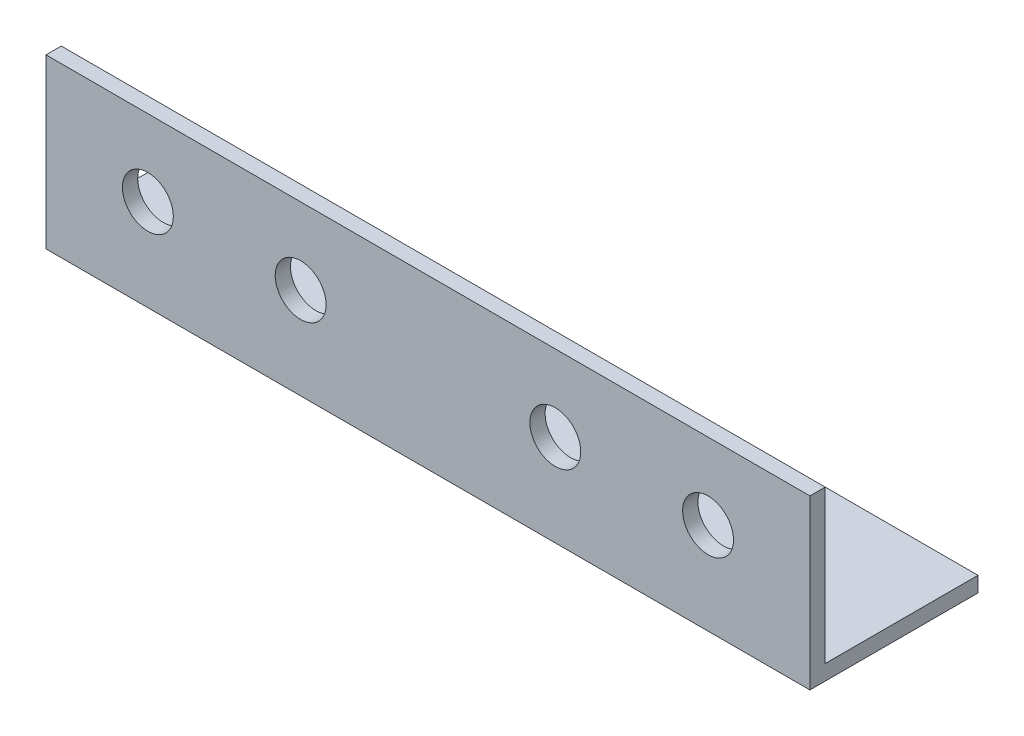
SolidWorks part; units mm, degrees
ref_plane "Спереди" through (0, 0, 0) normal (0, 0, 1) x (1, 0, 0)
ref_plane "Сверху" through (0, 0, 0) normal (0, 1, 0) x (1, 0, 0)
ref_plane "Справа" through (0, 0, 0) normal (1, 0, 0) x (0, 0, -1)
sketch "Эскиз1" plane through (0, 0, 0) normal (1, 0, 0) x (0, 0, -1)
  line L0 (0, 30) -> (0, 0)
  line L1 (0, 0) -> (30, 0)
extrude "Вытянуть-Тонкостенный1" add sketch "Эскиз1" along normal blind 150 thin thin type one direction wall 3
sketch "Эскиз2" plane through (0, 0, 0) normal (0, 0, -1) x (-1, 0, 0)
  line L2 (-75, 33.9302) -> (-75, -4.466) construction
  line L3 (-75, -9) -> (-75, -3) construction
  circle A0 centre (-130, 15) radius 5
  circle A1 centre (-100, 15) radius 5
  circle A2 centre (-50, 15) radius 5
  circle A3 centre (-20, 15) radius 5
  dimension "D1" = 2
extrude "Вырез-Вытянуть1" cut sketch "Эскиз2" against normal through all
